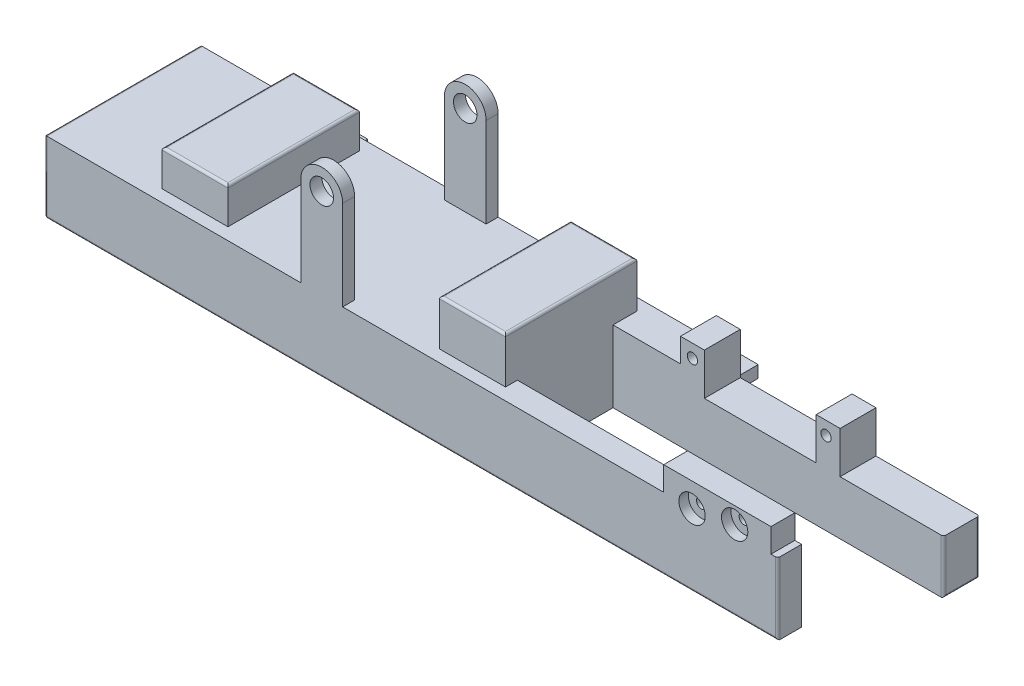
SolidWorks part; units mm, degrees
other "Markup1"
sketch "Sketch17" plane through (106.68, 38.735, 16.51) normal (0.2565, 0.8765, 0.4073) x (0.8462, 0, -0.5329)
ref_plane "Front" through (0, 0, 0) normal (0, 0, 1) x (1, 0, 0)
ref_plane "Top" through (0, 0, 0) normal (0, 1, 0) x (1, 0, 0)
ref_plane "Right" through (0, 0, 0) normal (1, 0, 0) x (0, 0, -1)
sketch "Sketch1" plane through (0, 0, 0) normal (0, 1, 0) x (1, 0, 0)
  line L0 (-58.8676, 16.51) -> (-58.8676, -16.51)
  line L1 (-106.68, 16.51) -> (106.68, 16.51)
  line L2 (-106.68, 16.51) -> (-106.68, -16.51)
  line L3 (-106.68, -16.51) -> (106.68, -16.51)
  line L4 (106.68, 16.51) -> (106.68, -16.51)
  line L5 (-106.68, 16.51) -> (106.68, -16.51) construction
  line L6 (-106.68, -16.51) -> (106.68, 16.51) construction
  line L7 (106.68, -16.51) -> (55.88, -16.51)
  line L8 (106.68, -16.51) -> (106.68, 8.89)
  line L9 (106.68, 8.89) -> (55.88, 8.89)
  line L10 (55.88, -16.51) -> (55.88, 8.89)
  line L11 (0, -55) -> (0, 55) construction
  line L12 (36.4884, 16.51) -> (46.4884, 16.51)
  line L13 (36.4884, 16.51) -> (36.4884, 29.718)
  line L14 (36.4884, 29.718) -> (46.4884, 29.718)
  line L15 (46.4884, 16.51) -> (46.4884, 29.718)
  line L16 (-36.4884, 29.718) -> (-46.4884, 29.718)
  line L17 (-46.4884, 16.51) -> (-46.4884, 29.718)
  line L18 (-36.4884, 16.51) -> (-46.4884, 16.51)
  line L19 (-36.4884, 16.51) -> (-36.4884, 29.718)
  line L21 (55.88, -16.51) -> (96.8527, -16.51)
  line L22 (55.88, -16.51) -> (55.88, -11.43)
  line L23 (55.88, -11.43) -> (96.8527, -11.43)
  line L24 (96.8527, -16.51) -> (96.8527, -11.43)
  circle A0 centre (-41.4884, 20.01) radius 2
  circle A1 centre (41.4884, 20.01) radius 2
  point P0 (0, 0)
  dimension "D7" = 4
  dimension "D1" = 213.36
  dimension "D2" = 33.02
  dimension "D3" = 25.4
  dimension "D4" = 50.8
  dimension "D5" = 10
  dimension "D6" = 13.208
  dimension "D8" = 5.08
extrude "Boss-Extrude1" add sketch "Sketch1" along normal blind 15.24 contours L3 L10 L9 L4 L1 L0 | L3 L24 L23 L10 region at (6.1788, 0, -1.1772) region at (76.3663, 0, 13.97)
sketch "Sketch3" plane through (0, 0, 16.51) normal (0, 0, 1) x (1, 0, 0)
  line L0 (4.445, 15.24) -> (-4.445, 15.24)
  line L1 (-58.8676, 15.24) -> (96.8527, 15.24) construction
  line L2 (-4.445, 15.24) -> (-4.445, 34.29)
  line L3 (4.445, 15.24) -> (4.445, 34.29)
  line L4 (0, -55) -> (0, 55) construction
  arc A0 (-4.445, 34.29) -> (4.445, 34.29) centre (0, 34.29) cw
  circle A1 centre (0, 34.29) radius 2.5
  point P8 (0, 15.24)
  dimension "D2" = 5
  dimension "D1" = 8.89
  dimension "D3" = 19.05
extrude "Boss-Extrude2" add sketch "Sketch3" against normal blind 2.54
mirror "Mirror1" about plane through (0, 0, 0) normal (0, 0, 1) of "Boss-Extrude2"
sketch "Sketch4" plane through (0, 15.24, 0) normal (0, 1, 0) x (1, 0, 0)
  line L0 (-21.3042, 0) -> (21.3042, 0) construction
  line L1 (22.4759, 13.9568) -> (36.4759, 13.9568)
  line L2 (22.4759, 13.9568) -> (22.4759, -13.9568)
  line L3 (22.4759, -13.9568) -> (36.4759, -13.9568)
  line L4 (36.4759, 13.9568) -> (36.4759, -13.9568)
  line L5 (0, -18.161) -> (0, 18.161) construction
  line L6 (-22.4759, -13.9568) -> (-36.4759, -13.9568)
  line L7 (-36.4759, 13.9568) -> (-36.4759, -13.9568)
  line L8 (-22.4759, 13.9568) -> (-36.4759, 13.9568)
  line L9 (-22.4759, 13.9568) -> (-22.4759, -13.9568)
  line L10 (-29.4759, 13.9568) -> (-29.4759, -13.9568) construction
  line L11 (29.4759, 13.9568) -> (29.4759, -13.9568) construction
  point P4 (22.4759, 0)
  dimension "D1" = 14
  dimension "D2" = 58.9518
extrude "Boss-Extrude3" add sketch "Sketch4" along normal blind 7.62
sketch "Sketch11" plane through (0, 22.86, 0) normal (0, 1, 0) x (1, 0, 0)
  line L4 (-36.4759, -13.9568) -> (-22.4759, -13.9568)
  line L5 (-36.4759, 13.9568) -> (-36.4759, -13.9568)
  line L6 (-22.4759, 13.9568) -> (-36.4759, 13.9568)
  line L7 (-22.4759, -13.9568) -> (-22.4759, 13.9568)
  line L8 (-36.4759, -13.9568) -> (-22.4759, -13.9568)
  line L9 (-36.4759, 13.9568) -> (-36.4759, -13.9568)
  line L10 (-22.4759, 13.9568) -> (-36.4759, 13.9568)
  line L11 (-22.4759, -13.9568) -> (-22.4759, 13.9568)
  line L12 (36.4759, 13.9568) -> (22.4759, 13.9568)
  line L13 (36.4759, -13.9568) -> (36.4759, 13.9568)
  line L14 (22.4759, -13.9568) -> (36.4759, -13.9568)
  line L15 (22.4759, 13.9568) -> (22.4759, -13.9568)
  line L16 (36.4759, 13.9568) -> (22.4759, 13.9568)
  line L17 (36.4759, -13.9568) -> (36.4759, 13.9568)
  line L18 (22.4759, -13.9568) -> (36.4759, -13.9568)
  line L19 (22.4759, 13.9568) -> (22.4759, -13.9568)
  dimension "D1" = 0
  dimension "D2" = 0
extrude "Boss-Extrude6" add sketch "Sketch11" along normal blind 2.0955 contours L16 L19 L18 L17
sketch "Sketch6" plane through (0, 22.86, 0) normal (0, 1, 0) x (1, 0, 0)
  line L1 (36.4759, 13.9568) -> (22.4759, 13.9568) construction
  line L4 (-22.4759, -13.9568) -> (-22.4759, 13.9568)
  line L5 (-22.4759, 13.9568) -> (-36.4759, 13.9568)
  line L6 (-36.4759, 13.9568) -> (-36.4759, -13.9568)
  line L7 (-36.4759, -13.9568) -> (-22.4759, -13.9568)
  line L8 (-22.4759, -13.9568) -> (-22.4759, 13.9568)
  line L9 (-22.4759, 13.9568) -> (-36.4759, 13.9568)
  line L10 (-36.4759, 13.9568) -> (-36.4759, -13.9568)
  line L11 (-36.4759, -13.9568) -> (-22.4759, -13.9568)
  circle A4 centre (-29.4759, 6.5433) radius 5.5
  circle A5 centre (29.4759, 6.5433) radius 5.5
  point P8 (-29.4759, 13.9568)
  point P14 (29.4759, 13.9568)
  dimension "D3" = 11
  dimension "D2" = 11
  dimension "D1" = 0
extrude "Cut-Extrude1" cut sketch "Sketch6" against normal blind 3 from offset 1.5 contours A4 offset against normal yes
fillet "Fillet1" radius 0.508 18 edges at (-58.8676, 15.24, 0) (-58.8676, 0, 0) (106.68, 0, -12.7) (106.68, 7.62, -8.89) (106.68, 7.62, -16.51) (-58.8676, 7.62, -16.51) (-58.8676, 7.62, 16.51) (18.9925, 0, 16.51) (-29.4759, 22.86, 13.9568) (-36.4759, 22.86, 0) (-29.4759, 22.86, -13.9568) (-22.4759, 22.86, 0) (29.4759, 24.9555, 13.9568) (22.4759, 24.9555, 0) (29.4759, 24.9555, -13.9568) (36.4759, 24.9555, 0) (106.68, 15.24, -12.7) (96.8527, 7.62, 16.51)
sketch "Sketch8" plane through (0, 15.24, 0) normal (0, 1, 0) x (1, 0, 0)
  line L0 (36.4759, 13.9568) -> (36.4759, -13.9568) construction
  line L1 (58.1514, 8.382) -> (58.1514, -16.002)
  line L3 (56.4759, 8.89) -> (36.4759, 8.89)
  line L4 (56.4759, 8.89) -> (56.4759, -11.43)
  line L5 (56.4759, -11.43) -> (36.4759, -11.43)
  line L6 (36.4759, 8.89) -> (36.4759, -11.43)
  line M44 (55.88, -11.43) -> (55.88, 8.89)
  line M46 (96.8527, -11.43) -> (55.88, -11.43)
  dimension "D1" = 20.32
  dimension "D3" = 20
extrude "Cut-Extrude2" cut sketch "Sketch8" against normal through all contours L3 L6 L5 L4 M46 M44 region at (46.178, 15.24, 1.27)
extrude "Boss-Extrude5" add sketch "Sketch1<3>" along normal blind 2.54 contours L1 L15 L14 L13 | L1 L19 L16 L17 region at (-41.4884, 0, -23.4404) region at (41.4884, 0, -23.4404)
sketch "Sketch1<3>" plane through (0, 0, 0) normal (0, 1, 0) x (1, 0, 0) same geometry as "Sketch1"
sketch "Sketch14" plane through (0, 0, -8.89) normal (0, 0, 1) x (1, 0, 0)
  line L0 (106.172, 15.24) -> (36.4759, 15.24) construction
  line L2 (106.68, 15.24) -> (106.68, 11.43)
  line L3 (106.68, 11.43) -> (55.88, 11.43)
  line L4 (55.88, 15.24) -> (55.88, 11.43)
  line L5 (106.68, 14.732) -> (106.68, 0.508) construction
  line L6 (55.88, 15.24) -> (106.68, 15.24)
  dimension "D1" = 3.81
  dimension "D4" = 50.8
extrude "Cut-Extrude5" cut sketch "Sketch14" against normal through all and the other way blind 9.2075
sketch "Sketch15" plane through (0, 0, -8.89) normal (0, 0, 1) x (1, 0, 0)
  line L0 (55.88, 15.24) -> (36.4759, 15.24) construction
  line L1 (50.8, 15.24) -> (55.88, 15.24)
  line L2 (50.8, 15.24) -> (50.8, 20.32)
  line L3 (50.8, 20.32) -> (55.88, 20.32)
  line L4 (55.88, 15.24) -> (55.88, 20.32)
  line L5 (106.172, 11.43) -> (55.88, 11.43) construction
  line L6 (79.629, 11.43) -> (84.709, 11.43)
  line L7 (79.629, 11.43) -> (79.629, 20.32)
  line L8 (79.629, 20.32) -> (84.709, 20.32)
  line L9 (84.709, 11.43) -> (84.709, 20.32)
  line L11 (55.88, 11.43) -> (55.88, 15.24) construction
  dimension "D1" = 5.08
  dimension "D2" = 23.749
  dimension "D3" = 5.08
  dimension "D4" = 5.08
extrude "Boss-Extrude7" add sketch "Sketch15" against normal up to vertex (7.62 mm away) up to point (55.88, 15.24, -16.51)
sketch "Sketch16" plane through (0, 0, -8.89) normal (0, 0, 1) x (1, 0, 0)
  line L0 (55.88, 11.43) -> (55.88, 20.32) construction
  line L1 (106.172, 11.43) -> (84.709, 11.43) construction
  circle A0 centre (53.34, 17.526) radius 1.0922
  circle A1 centre (81.7245, 17.526) radius 1.0922
  dimension "D1" = 2.1844
  dimension "D2" = 2.54
  dimension "D3" = 6.096
  dimension "D4" = 28.3845
extrude "Cut-Extrude6" cut sketch "Sketch16" against normal up to next
sketch "Sketch18" plane through (0, 15.24, 0) normal (0, 1, 0) x (1, 0, 0)
  line L0 (36.4759, -11.43) -> (96.8527, -11.43) construction
  line L1 (95.4237, -11.43) -> (72.6409, -11.43)
  line L2 (95.4237, -11.43) -> (95.4237, -16.51)
  line L3 (95.4237, -16.51) -> (72.6409, -16.51)
  line L4 (72.6409, -11.43) -> (72.6409, -16.51)
  line L5 (4.445, -16.51) -> (96.3447, -16.51) construction
extrude "Boss-Extrude8" add sketch "Sketch18" along normal blind 5.08
sketch "Sketch9" plane through (0, 0, 11.43) normal (0, 0, -1) x (-1, 0, 0)
  line L0 (-87.7134, 16.8367) -> (-78.6583, 15.24) construction
  line L2 (25.4254, 0) -> (-25.4254, 0) construction
  circle A0 centre (-87.7134, 16.8367) radius 1.05
  circle A1 centre (-78.6583, 15.24) radius 1.05
  dimension "D1" = 2.1
  dimension "D4" = 15.24
  dimension "D2" = 9.1948
  dimension "D3" = 10
extrude "Cut-Extrude3" cut sketch "Sketch9" along normal blind 12.7 and the other way blind 12.7
sketch "Sketch10" plane through (0, 0, 16.51) normal (0, 0, 1) x (1, 0, 0)
  circle A0 centre (78.6583, 15.24) radius 2.794
  circle A1 centre (87.7134, 16.8367) radius 2.794
  circle M2 centre (87.7134, 16.8367) radius 1.05
  circle M3 centre (78.6583, 15.24) radius 1.05
  dimension "D1" = 5.588
extrude "Cut-Extrude4" cut sketch "Sketch10" against normal blind 2 contours A0 M3 | A1 M2 region at (75.9434, 15.24, 16.51) region at (84.9985, 16.8367, 16.51)
sketch "Sketch19" plane through (0, 24.9555, 0) normal (0, 1, 0) x (1, 0, 0)
  line L0 (36.4759, 13.9568) -> (22.4759, 13.9568) construction
  line L1 (36.4759, 13.9568) -> (22.4759, 13.9568)
  circle A0 centre (29.4759, 6.5433) radius 5.5
  circle A1 centre (-29.4759, 6.5433) radius 5.5 construction
  circle A2 centre (-29.4759, 6.5433) radius 5.5
  point P8 (29.4759, 13.9568)
extrude "Cut-Extrude7" cut sketch "Sketch19" against normal blind 3.5 from offset 1 contours A0 offset against normal yes
